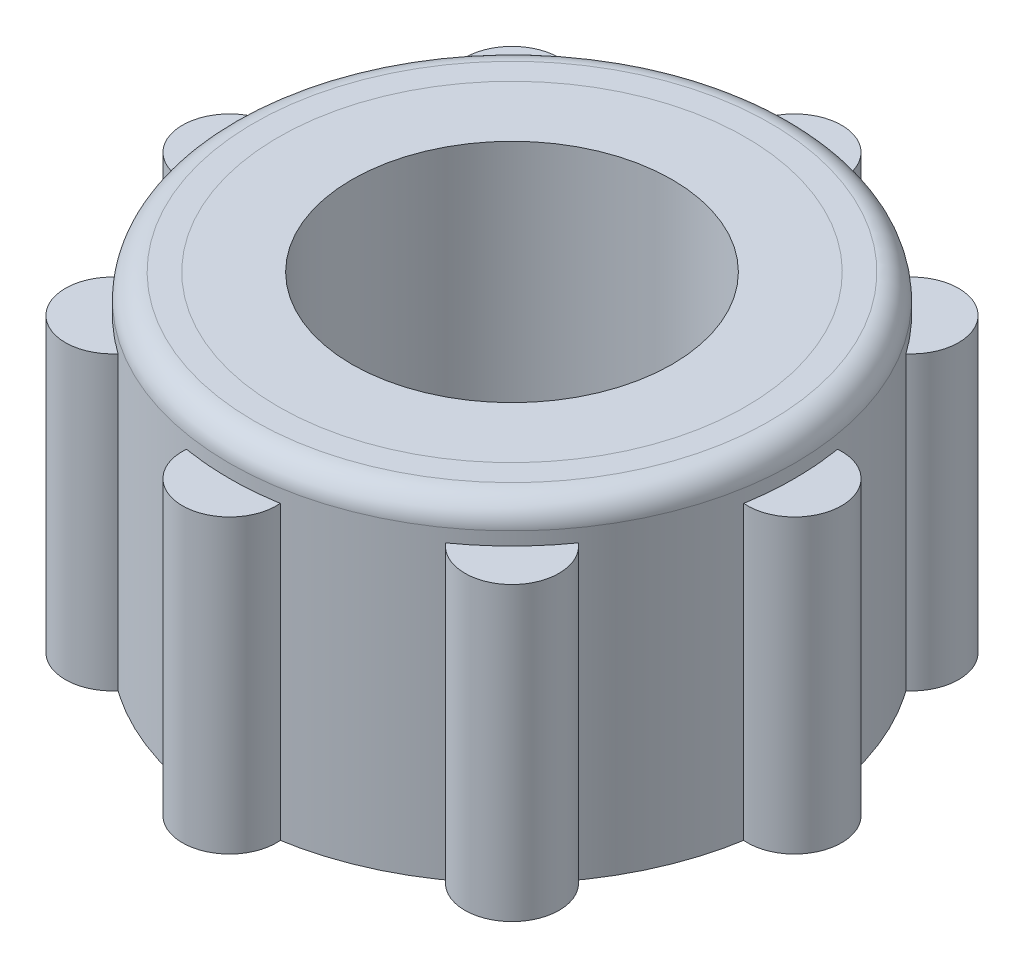
SolidWorks part; units mm, degrees
ref_plane "Front Plane" through (0, 0, 0) normal (0, 0, 1) x (1, 0, 0)
ref_plane "Top Plane" through (0, 0, 0) normal (0, 1, 0) x (1, 0, 0)
ref_plane "Right Plane" through (0, 0, 0) normal (1, 0, 0) x (0, 0, -1)
sketch "Sketch2" plane through (0, 0, 0) normal (0, 1, 0) x (1, 0, 0)
  circle A0 centre (0, 0) radius 30
  circle A1 centre (0, 0) radius 17
  circle A2 centre (0, 0) radius 24.8
  arc A7 (-29.5833, 4.9826) -> (-29.5833, -4.9826) centre (-30, 0) ccw
  circle A8 centre (0, 0) radius 30
  arc A9 (-4.9826, -29.5833) -> (4.9826, -29.5833) centre (0, -30) ccw
  circle A10 centre (0, 0) radius 30
  arc A11 (29.5833, -4.9826) -> (29.5833, 4.9826) centre (30, 0) ccw
  circle A12 centre (0, 0) radius 30
  arc A13 (-17.3953, 24.4418) -> (-24.4418, 17.3953) centre (-21.2132, 21.2132) ccw
  arc A14 (4.9826, 29.5833) -> (-4.9826, 29.5833) centre (0, 30) ccw
  arc A15 (24.4418, 17.3953) -> (17.3953, 24.4418) centre (21.2132, 21.2132) ccw
  arc A16 (29.5833, -4.9826) -> (29.5833, 4.9826) centre (30, 0) ccw
  arc A17 (17.3953, -24.4418) -> (24.4418, -17.3953) centre (21.2132, -21.2132) ccw
  arc A18 (-4.9826, -29.5833) -> (4.9826, -29.5833) centre (0, -30) ccw
  arc A19 (-24.4418, -17.3953) -> (-17.3953, -24.4418) centre (-21.2132, -21.2132) ccw
  dimension "D1" = 60
  dimension "D2" = 34
  dimension "D3" = 49.6
  dimension "D4" = 4
  dimension "D6" = 5
  dimension "D5" = 8
extrude "Boss-Extrude1" add sketch "Sketch2" along normal blind 35 contours A0 A12 A8 A10 A2 region at (29.0501, 0, 2.4293)
extrude "Boss-Extrude2" add sketch "Sketch2<8>" along normal blind 31 separate body contours A8 A9 | A12 A17 | A10 A11 | A12 A15 | A12 A19 | A12 A14 | A0 A7 | A12 A13 region at (32.0453, 0, 0) region at (22.6594, 0, -22.6594) region at (22.6594, 0, 22.6594) region at (0, 0, -32.0453) region at (0, 0, 32.0453) region at (-22.6594, 0, -22.6594) region at (-22.6594, 0, 22.6594) region at (-32.0453, 0, 0)
sketch "Sketch2<8>" plane through (0, 0, 0) normal (0, 1, 0) x (1, 0, 0) same geometry as "Sketch2"
extrude "Boss-Extrude4" add sketch "Sketch2<11>" along normal blind 35 separate body contours A2 A1 region at (-24.0986, 0, 0)
sketch "Sketch2<11>" plane through (0, 0, 0) normal (0, 1, 0) x (1, 0, 0) same geometry as "Sketch2"
fillet "Fillet5" radius 2.6 1 edges at (0, 35, 30)
